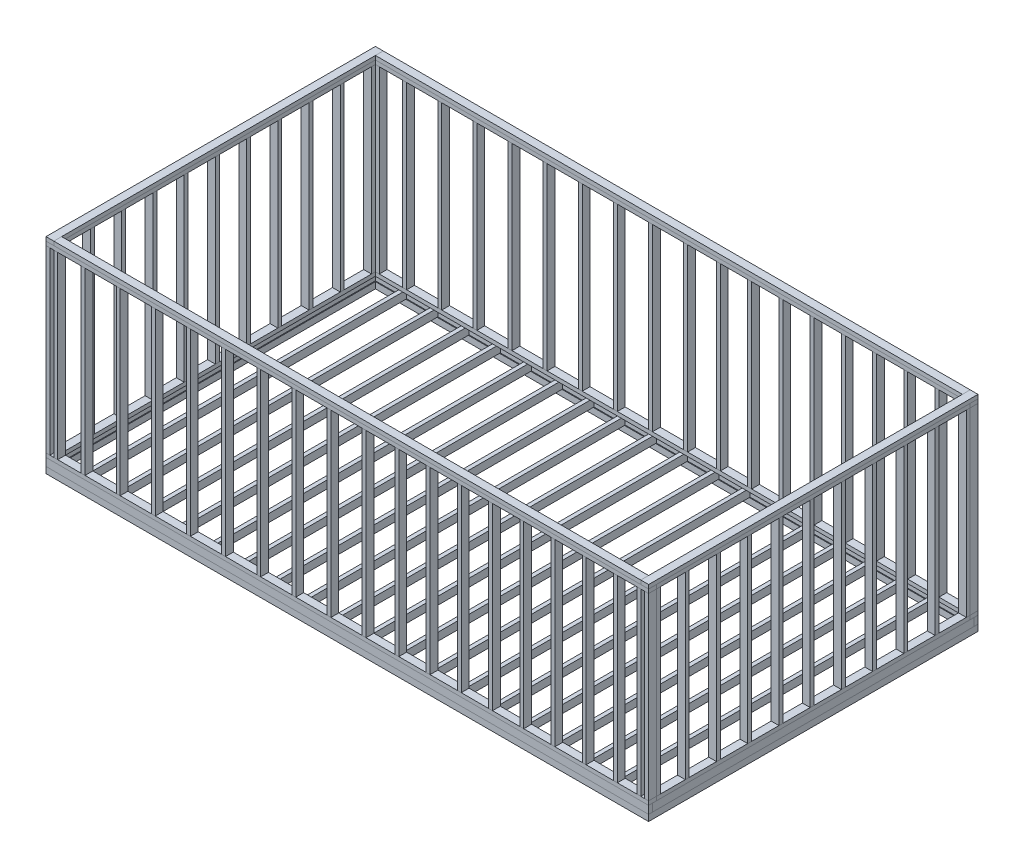
SolidWorks part; units mm, degrees
ref_plane "Front Plane" through (0, 0, 0) normal (0, 0, 1) x (1, 0, 0)
ref_plane "Top Plane" through (0, 0, 0) normal (0, 1, 0) x (1, 0, 0)
ref_plane "Right Plane" through (0, 0, 0) normal (1, 0, 0) x (0, 0, -1)
other "Configuration Table"
sketch "Metal Base" plane through (0, 0, 0) normal (0, 1, 0) x (1, 0, 0)
  line L1 (0, 0) -> (7600, 0)
  line L2 (0, 0) -> (0, 4100)
  line L3 (0, 4100) -> (7600, 4100)
  line L4 (7600, 0) -> (7600, 4100)
  dimension "D1" = 4100
  dimension "D2" = 7600
sketch "Furniture" plane through (0, 0, 0) normal (0, 1, 0) x (1, 0, 0)
  line L0 (6900, 2000) -> (6900, 4100)
  line L1 (2195.453, 2408.8005) -> (1395.453, 2408.8005)
  line L2 (2195.453, 2408.8005) -> (2195.453, 3908.8005)
  line L3 (2195.453, 3908.8005) -> (1395.453, 3908.8005)
  line L4 (1395.453, 2408.8005) -> (1395.453, 3908.8005)
  line L5 (1095.7475, 72.998) -> (95.7475, 72.998)
  line L6 (1095.7475, 72.998) -> (1095.7475, 2072.998)
  line L7 (1095.7475, 2072.998) -> (95.7475, 2072.998)
  line L8 (95.7475, 72.998) -> (95.7475, 2072.998)
  line L9 (0, 0) -> (0, 4100) construction
  line L10 (2300, 4100) -> (2300, 0)
  line L11 (0, 0) -> (7600, 0) construction
  line L12 (6400, 0) -> (6400, 2000)
  line L13 (0, 4100) -> (7600, 4100) construction
  line L14 (6400, 2000) -> (7600, 2000)
  line L15 (2300, 2050) -> (7946.9663, 2050) construction
  line L16 (7600, 0) -> (7600, 4100) construction
  line L17 (2079.5569, 869.0285) -> (2300, 100)
  line L18 (6400, 100) -> (6911.6082, 577.7625)
  line L19 (6590.3736, 1221.8512) -> (7190.3736, 1221.8512)
  line L24 (6590.3736, 1221.8512) -> (6590.3736, 1981.8512)
  line L25 (6590.3736, 1981.8512) -> (7190.3736, 1981.8512)
  line L26 (7190.3736, 1221.8512) -> (7190.3736, 1981.8512)
  line L27 (6400, 2000) -> (5800, 2000)
  line L28 (6400, 2000) -> (6400, 1400)
  line L29 (6400, 1400) -> (5800, 1400)
  line L30 (5800, 2000) -> (5800, 1400)
  line L31 (2300, 2050) -> (4300, 2050)
  line L32 (4300, 2050) -> (4300, 4100)
  line L33 (2300, 100) -> (2579.3532, 100) construction
  line L34 (2579.3532, 100) -> (2579.3532, 981.1813) construction
  line L35 (2579.3532, 981.1813) -> (2300, 981.1813) construction
  arc A1 (2079.5569, 869.0285) -> (1506.2746, 0) centre (2300, 100) ccw construction
  arc A2 (6911.6082, 577.7625) -> (6400, 800) centre (6400, 100) ccw construction
  dimension "D13" = 600
  dimension "D1" = 1500
  dimension "D2" = 800
  dimension "D3" = 2000
  dimension "D4" = 1000
  dimension "D5" = 2000
  dimension "D6" = 1200
  dimension "D7" = 700
  dimension "D8" = 600
  dimension "D9" = 2300
  dimension "D10" = 800
  dimension "D11" = 100
  dimension "D12" = 760
  dimension "D14" = 100
  dimension "D15" = 700
  dimension "D16" = 2100
  dimension "D17" = 600
  dimension "D18" = 4100
  dimension "D19" = 4100
  dimension "D20" = 2000
  dimension "D21" = 2050
sketch "Metal frame" plane through (0, 0, 0) normal (0, 1, 0) x (1, 0, 0)
  line L0 (0, 4100) -> (7600, 4100) construction
  line L1 (0, 4100) -> (7600, 4100)
  line L2 (0, 0) -> (0, 4100) construction
  line L3 (0, 0) -> (0, 4100)
  line L4 (0, 0) -> (7600, 0) construction
  line L5 (0, 0) -> (7600, 0)
  line L6 (7600, 0) -> (7600, 4100) construction
  line L7 (7600, 0) -> (7600, 4100)
  line L8 (-60, 4160) -> (7660, 4160)
  line L9 (7660, -60) -> (7660, 4160)
  line L10 (-60, -60) -> (7660, -60)
  line L11 (-60, -60) -> (-60, 4160)
  dimension "D2" = 7720
  dimension "D3" = 4220
  dimension "D1" = 60
sketch "Walls bottom" plane through (0, 0, 0) normal (0, 1, 0) x (1, 0, 0)
  line L0 (-60, 4160) -> (7660, 4160) construction
  line L2 (-60, -60) -> (7660, -60) construction
  line L3 (7660, -60) -> (7660, 4160) construction
  line L4 (-60, -60) -> (-60, 4160) construction
  line L5 (-60, -60) -> (7660, -60)
  line L6 (7660, -60) -> (7660, 4160)
  line L7 (-60, 4160) -> (7660, 4160)
  line L8 (-60, -60) -> (-60, 4160)
  line L9 (40, 40) -> (40, 4060)
  line L10 (40, 4060) -> (7560, 4060)
  line L11 (7560, 40) -> (7560, 4060)
  line L12 (40, 40) -> (7560, 40)
  dimension "D2" = 4020
  dimension "D3" = 7520
  dimension "D4" = 7720
  dimension "D5" = 4220
  dimension "D1" = 100
extrude "Boss-Extrude1" add sketch "Metal frame" against normal blind 80
sketch "Sketch4" plane through (0, 0, 0) normal (0, 1, 0) x (1, 0, 0)
  line L1 (-60, 4160) -> (7660, 4160)
  line L2 (-60, 4160) -> (-60, 4110)
  line L3 (-60, 4110) -> (7660, 4110)
  line L4 (7660, 4160) -> (7660, 4110)
  line L5 (7660, -60) -> (7660, 4160) construction
  line L7 (7660, 4110) -> (7610, 4110)
  line L8 (7660, 4110) -> (7660, -10)
  line L9 (7660, -10) -> (7610, -10)
  line L10 (7610, 4110) -> (7610, -10)
  line L11 (7660, -10) -> (-60, -10)
  line L12 (7660, -10) -> (7660, -60)
  line L13 (7660, -60) -> (-60, -60)
  line L14 (-60, -10) -> (-60, -60)
  line L15 (-60, -10) -> (-10, -10)
  line L16 (-60, -10) -> (-60, 4110)
  line L17 (-60, 4110) -> (-10, 4110)
  line L18 (-10, -10) -> (-10, 4110)
  line M13 (-60, 4160) -> (-60, -60)
  line M14 (-60, -60) -> (7660, -60)
  line M15 (7660, -60) -> (7660, 4160)
  line M16 (7660, 4160) -> (-60, 4160)
  dimension "D1" = 50
  dimension "D2" = 50
  dimension "D3" = 50
  dimension "D4" = 50
extrude "Boss-Extrude2" add sketch "Sketch4" along normal blind 100 separate body contours L3 M13 M15 M16 | L9 L11 M13 M14 M15 region at (3800, 0, -4135) region at (3800, 0, 35)
extrude "Boss-Extrude3" add sketch "Sketch4<3>" along normal blind 100 separate body contours L11 L18 L3 M13 | L3 L10 L9 M15 region at (-35, 0, -2050) region at (7635, 0, -2050)
sketch "Sketch4<3>" plane through (0, 0, 0) normal (0, 1, 0) x (1, 0, 0) same geometry as "Sketch4"
pattern_linear "LPattern1" count 20 spacing 400 along (1, 0, 0) of bodies 106
sketch "Sketch5" plane through (0, 100, 0) normal (0, 1, 0) x (1, 0, 0)
  line L0 (7660, -10) -> (7660, 4110) construction
  line L1 (-60, 4160) -> (7660, 4160)
  line L2 (-60, 4160) -> (-60, 4060)
  line L3 (-60, 4060) -> (7660, 4060)
  line L4 (7660, 4160) -> (7660, 4060)
  line L10 (7660, 4060) -> (7560, 4060)
  line L11 (7660, 4060) -> (7660, 40)
  line L12 (7660, 40) -> (7560, 40)
  line L13 (7560, 4060) -> (7560, 40)
  line L14 (-60, 4060) -> (40, 4060)
  line L15 (-60, 4060) -> (-60, 40)
  line L16 (-60, 40) -> (40, 40)
  line L17 (40, 4060) -> (40, 40)
  line L18 (-60, -60) -> (7660, -60)
  line L19 (-60, -60) -> (-60, 40)
  line L20 (-60, 40) -> (7660, 40)
  line L21 (7660, -60) -> (7660, 40)
  line M9 (7660, -10) -> (-60, -10)
  line M10 (-60, -10) -> (-60, -60)
  line M11 (-60, -60) -> (7660, -60)
  line M12 (7660, -60) -> (7660, -10)
  dimension "D1" = 100
  dimension "D2" = 100
  dimension "D3" = 100
  dimension "D4" = 100
extrude "Boss-Extrude4" add sketch "Sketch5" along normal blind 50 separate body contours L21 L12 L20 L16 L19 M9 | M12 M9 M10 M11 | L4 L1 L2 L3 region at (3800, 100, -4110) region at (3800, 100, -15) region at (3800, 100, 35)
extrude "Boss-Extrude5" add sketch "Sketch5<4>" along normal blind 50 separate body contours L3 L13 L12 L11 | L17 L3 L15 L16 region at (-10, 100, -2050) region at (7610, 100, -2050)
sketch "Sketch5<4>" plane through (0, 100, 0) normal (0, 1, 0) x (1, 0, 0) same geometry as "Sketch5"
sketch "Sketch6" plane through (0, 150, 0) normal (0, 1, 0) x (1, 0, 0)
  line L0 (7660, 40) -> (-60, 40) construction
  line L1 (-60, -60) -> (-10, -60)
  line L2 (-60, -60) -> (-60, 40)
  line L3 (-60, 40) -> (-10, 40)
  line L4 (-10, -60) -> (-10, 40)
  line L5 (-60, 4060) -> (40, 4060) construction
  line L6 (-60, 4160) -> (-10, 4160)
  line L7 (-60, 4160) -> (-60, 4060)
  line L8 (-60, 4060) -> (-10, 4060)
  line L9 (-10, 4160) -> (-10, 4060)
  line L10 (390, -60) -> (390, 40)
  line L11 (390, -60) -> (440, -60)
  line L12 (440, -60) -> (440, 40)
  line L13 (390, 40) -> (440, 40)
  line L14 (390, 4160) -> (390, 4060)
  line L15 (390, 4160) -> (440, 4160)
  line L16 (440, 4160) -> (440, 4060)
  line L17 (390, 4060) -> (440, 4060)
  line L18 (840, -60) -> (840, 40)
  line L19 (840, -60) -> (890, -60)
  line L20 (890, -60) -> (890, 40)
  line L21 (840, 40) -> (890, 40)
  line L22 (840, 4160) -> (840, 4060)
  line L23 (840, 4160) -> (890, 4160)
  line L24 (890, 4160) -> (890, 4060)
  line L25 (840, 4060) -> (890, 4060)
  line L26 (1290, -60) -> (1290, 40)
  line L27 (1290, -60) -> (1340, -60)
  line L28 (1340, -60) -> (1340, 40)
  line L29 (1290, 40) -> (1340, 40)
  line L30 (1290, 4160) -> (1290, 4060)
  line L31 (1290, 4160) -> (1340, 4160)
  line L32 (1340, 4160) -> (1340, 4060)
  line L33 (1290, 4060) -> (1340, 4060)
  line L34 (1740, -60) -> (1740, 40)
  line L35 (1740, -60) -> (1790, -60)
  line L36 (1790, -60) -> (1790, 40)
  line L37 (1740, 40) -> (1790, 40)
  line L38 (1740, 4160) -> (1740, 4060)
  line L39 (1740, 4160) -> (1790, 4160)
  line L40 (1790, 4160) -> (1790, 4060)
  line L41 (1740, 4060) -> (1790, 4060)
  line L42 (2190, -60) -> (2190, 40)
  line L43 (2190, -60) -> (2240, -60)
  line L44 (2240, -60) -> (2240, 40)
  line L45 (2190, 40) -> (2240, 40)
  line L46 (2190, 4160) -> (2190, 4060)
  line L47 (2190, 4160) -> (2240, 4160)
  line L48 (2240, 4160) -> (2240, 4060)
  line L49 (2190, 4060) -> (2240, 4060)
  line L50 (2640, -60) -> (2640, 40)
  line L51 (2640, -60) -> (2690, -60)
  line L52 (2690, -60) -> (2690, 40)
  line L53 (2640, 40) -> (2690, 40)
  line L54 (2640, 4160) -> (2640, 4060)
  line L55 (2640, 4160) -> (2690, 4160)
  line L56 (2690, 4160) -> (2690, 4060)
  line L57 (2640, 4060) -> (2690, 4060)
  line L58 (3090, -60) -> (3090, 40)
  line L59 (3090, -60) -> (3140, -60)
  line L60 (3140, -60) -> (3140, 40)
  line L61 (3090, 40) -> (3140, 40)
  line L62 (3090, 4160) -> (3090, 4060)
  line L63 (3090, 4160) -> (3140, 4160)
  line L64 (3140, 4160) -> (3140, 4060)
  line L65 (3090, 4060) -> (3140, 4060)
  line L66 (3540, -60) -> (3540, 40)
  line L67 (3540, -60) -> (3590, -60)
  line L68 (3590, -60) -> (3590, 40)
  line L69 (3540, 40) -> (3590, 40)
  line L70 (3540, 4160) -> (3540, 4060)
  line L71 (3540, 4160) -> (3590, 4160)
  line L72 (3590, 4160) -> (3590, 4060)
  line L73 (3540, 4060) -> (3590, 4060)
  line L74 (3990, -60) -> (3990, 40)
  line L75 (3990, -60) -> (4040, -60)
  line L76 (4040, -60) -> (4040, 40)
  line L77 (3990, 40) -> (4040, 40)
  line L78 (3990, 4160) -> (3990, 4060)
  line L79 (3990, 4160) -> (4040, 4160)
  line L80 (4040, 4160) -> (4040, 4060)
  line L81 (3990, 4060) -> (4040, 4060)
  line L82 (7560, 4060) -> (7660, 4060) construction
  line L83 (7660, 4160) -> (7610, 4160)
  line L84 (7660, 4160) -> (7660, 4060)
  line L85 (7660, 4060) -> (7610, 4060)
  line L86 (7610, 4160) -> (7610, 4060)
  line L87 (7660, 40) -> (7560, 40) construction
  line L88 (7660, -60) -> (7610, -60)
  line L89 (7660, -60) -> (7660, 40)
  line L90 (7660, 40) -> (7610, 40)
  line L91 (7610, -60) -> (7610, 40)
  line L92 (7260, -60) -> (7260, 40)
  line L93 (7260, -60) -> (7210, -60)
  line L94 (7210, -60) -> (7210, 40)
  line L95 (7260, 40) -> (7210, 40)
  line L96 (7260, 4160) -> (7260, 4060)
  line L97 (7260, 4160) -> (7210, 4160)
  line L98 (7210, 4160) -> (7210, 4060)
  line L99 (7260, 4060) -> (7210, 4060)
  line L100 (6860, -60) -> (6860, 40)
  line L101 (6860, -60) -> (6810, -60)
  line L102 (6810, -60) -> (6810, 40)
  line L103 (6860, 40) -> (6810, 40)
  line L104 (6860, 4160) -> (6860, 4060)
  line L105 (6860, 4160) -> (6810, 4160)
  line L106 (6810, 4160) -> (6810, 4060)
  line L107 (6860, 4060) -> (6810, 4060)
  line L108 (6460, -60) -> (6460, 40)
  line L109 (6460, -60) -> (6410, -60)
  line L110 (6410, -60) -> (6410, 40)
  line L111 (6460, 40) -> (6410, 40)
  line L112 (6460, 4160) -> (6460, 4060)
  line L113 (6460, 4160) -> (6410, 4160)
  line L114 (6410, 4160) -> (6410, 4060)
  line L115 (6460, 4060) -> (6410, 4060)
  line L116 (6060, -60) -> (6060, 40)
  line L117 (6060, -60) -> (6010, -60)
  line L118 (6010, -60) -> (6010, 40)
  line L119 (6060, 40) -> (6010, 40)
  line L120 (6060, 4160) -> (6060, 4060)
  line L121 (6060, 4160) -> (6010, 4160)
  line L122 (6010, 4160) -> (6010, 4060)
  line L123 (6060, 4060) -> (6010, 4060)
  line L124 (5660, -60) -> (5660, 40)
  line L125 (5660, -60) -> (5610, -60)
  line L126 (5610, -60) -> (5610, 40)
  line L127 (5660, 40) -> (5610, 40)
  line L128 (5660, 4160) -> (5660, 4060)
  line L129 (5660, 4160) -> (5610, 4160)
  line L130 (5610, 4160) -> (5610, 4060)
  line L131 (5660, 4060) -> (5610, 4060)
  line L132 (5260, -60) -> (5260, 40)
  line L133 (5260, -60) -> (5210, -60)
  line L134 (5210, -60) -> (5210, 40)
  line L135 (5260, 40) -> (5210, 40)
  line L136 (5260, 4160) -> (5260, 4060)
  line L137 (5260, 4160) -> (5210, 4160)
  line L138 (5210, 4160) -> (5210, 4060)
  line L139 (5260, 4060) -> (5210, 4060)
  line L140 (4860, -60) -> (4860, 40)
  line L141 (4860, -60) -> (4810, -60)
  line L142 (4810, -60) -> (4810, 40)
  line L143 (4860, 40) -> (4810, 40)
  line L144 (4860, 4160) -> (4860, 4060)
  line L145 (4860, 4160) -> (4810, 4160)
  line L146 (4810, 4160) -> (4810, 4060)
  line L147 (4860, 4060) -> (4810, 4060)
  line L148 (4460, -60) -> (4460, 40)
  line L149 (4460, -60) -> (4410, -60)
  line L150 (4410, -60) -> (4410, 40)
  line L151 (4460, 40) -> (4410, 40)
  line L152 (4460, 4160) -> (4460, 4060)
  line L153 (4460, 4160) -> (4410, 4160)
  line L154 (4410, 4160) -> (4410, 4060)
  line L155 (4460, 4060) -> (4410, 4060)
  dimension "D1" = 50
  dimension "D2" = 10
  dimension "D3" = 9
extrude "Boss-Extrude6" add sketch "Sketch6" along normal blind 2300 separate body
sketch "Sketch7" plane through (0, 150, 0) normal (0, 1, 0) x (1, 0, 0)
  line L0 (40, 4060) -> (40, 40) construction
  line L1 (-60, 4060) -> (40, 4060)
  line L2 (-60, 4060) -> (-60, 4010)
  line L3 (-60, 4010) -> (40, 4010)
  line L4 (40, 4060) -> (40, 4010)
  line L5 (7660, 4060) -> (7660, 40) construction
  line L6 (7560, 4060) -> (7660, 4060)
  line L7 (7560, 4060) -> (7560, 4010)
  line L8 (7560, 4010) -> (7660, 4010)
  line L9 (7660, 4060) -> (7660, 4010)
  line L10 (-60, 3660) -> (-60, 3610)
  line L11 (-60, 3660) -> (40, 3660)
  line L12 (40, 3660) -> (40, 3610)
  line L13 (-60, 3610) -> (40, 3610)
  line L14 (7560, 3660) -> (7560, 3610)
  line L15 (7560, 3660) -> (7660, 3660)
  line L16 (7660, 3660) -> (7660, 3610)
  line L17 (7560, 3610) -> (7660, 3610)
  line L18 (-60, 3260) -> (-60, 3210)
  line L19 (-60, 3260) -> (40, 3260)
  line L20 (40, 3260) -> (40, 3210)
  line L21 (-60, 3210) -> (40, 3210)
  line L22 (7560, 3260) -> (7560, 3210)
  line L23 (7560, 3260) -> (7660, 3260)
  line L24 (7660, 3260) -> (7660, 3210)
  line L25 (7560, 3210) -> (7660, 3210)
  line L26 (-60, 2860) -> (-60, 2810)
  line L27 (-60, 2860) -> (40, 2860)
  line L28 (40, 2860) -> (40, 2810)
  line L29 (-60, 2810) -> (40, 2810)
  line L30 (7560, 2860) -> (7560, 2810)
  line L31 (7560, 2860) -> (7660, 2860)
  line L32 (7660, 2860) -> (7660, 2810)
  line L33 (7560, 2810) -> (7660, 2810)
  line L34 (-60, 2460) -> (-60, 2410)
  line L35 (-60, 2460) -> (40, 2460)
  line L36 (40, 2460) -> (40, 2410)
  line L37 (-60, 2410) -> (40, 2410)
  line L38 (7560, 2460) -> (7560, 2410)
  line L39 (7560, 2460) -> (7660, 2460)
  line L40 (7660, 2460) -> (7660, 2410)
  line L41 (7560, 2410) -> (7660, 2410)
  line L42 (-60, 2060) -> (-60, 2010)
  line L43 (-60, 2060) -> (40, 2060)
  line L44 (40, 2060) -> (40, 2010)
  line L45 (-60, 2010) -> (40, 2010)
  line L46 (7560, 2060) -> (7560, 2010)
  line L47 (7560, 2060) -> (7660, 2060)
  line L48 (7660, 2060) -> (7660, 2010)
  line L49 (7560, 2010) -> (7660, 2010)
  line L50 (-60, 1660) -> (-60, 1610)
  line L51 (-60, 1660) -> (40, 1660)
  line L52 (40, 1660) -> (40, 1610)
  line L53 (-60, 1610) -> (40, 1610)
  line L54 (7560, 1660) -> (7560, 1610)
  line L55 (7560, 1660) -> (7660, 1660)
  line L56 (7660, 1660) -> (7660, 1610)
  line L57 (7560, 1610) -> (7660, 1610)
  line L58 (-60, 1260) -> (-60, 1210)
  line L59 (-60, 1260) -> (40, 1260)
  line L60 (40, 1260) -> (40, 1210)
  line L61 (-60, 1210) -> (40, 1210)
  line L62 (7560, 1260) -> (7560, 1210)
  line L63 (7560, 1260) -> (7660, 1260)
  line L64 (7660, 1260) -> (7660, 1210)
  line L65 (7560, 1210) -> (7660, 1210)
  line L66 (-60, 860) -> (-60, 810)
  line L67 (-60, 860) -> (40, 860)
  line L68 (40, 860) -> (40, 810)
  line L69 (-60, 810) -> (40, 810)
  line L70 (7560, 860) -> (7560, 810)
  line L71 (7560, 860) -> (7660, 860)
  line L72 (7660, 860) -> (7660, 810)
  line L73 (7560, 810) -> (7660, 810)
  line L74 (-60, 460) -> (-60, 410)
  line L75 (-60, 460) -> (40, 460)
  line L76 (40, 460) -> (40, 410)
  line L77 (-60, 410) -> (40, 410)
  line L78 (7560, 460) -> (7560, 410)
  line L79 (7560, 460) -> (7660, 460)
  line L80 (7660, 460) -> (7660, 410)
  line L81 (7560, 410) -> (7660, 410)
  dimension "D1" = 50
  dimension "D2" = 10
extrude "Boss-Extrude7" add sketch "Sketch7" along normal blind 2300 separate body
sketch "Sketch8" plane through (0, 150, 0) normal (0, 1, 0) x (1, 0, 0)
  line L0 (40, 4060) -> (40, 40) construction
  line L1 (-60, 40) -> (40, 40)
  line L2 (-60, 40) -> (-60, 90)
  line L3 (-60, 90) -> (40, 90)
  line L4 (40, 40) -> (40, 90)
  line L5 (7560, 4060) -> (7560, 40) construction
  line L6 (7660, 40) -> (7560, 40)
  line L7 (7660, 40) -> (7660, 90)
  line L8 (7660, 90) -> (7560, 90)
  line L9 (7560, 40) -> (7560, 90)
  line L10 (-60, -60) -> (7660, -60) construction
  line L11 (7560, 40) -> (7510, 40)
  line L12 (7560, 40) -> (7560, -60)
  line L13 (7560, -60) -> (7510, -60)
  line L14 (7510, 40) -> (7510, -60)
  line L15 (-60, 4160) -> (7660, 4160) construction
  line L16 (40, 40) -> (90, 40)
  line L17 (40, 40) -> (40, -60)
  line L18 (40, -60) -> (90, -60)
  line L19 (90, 40) -> (90, -60)
  line L20 (40, 4060) -> (90, 4060)
  line L21 (40, 4060) -> (40, 4160)
  line L22 (40, 4160) -> (90, 4160)
  line L23 (90, 4060) -> (90, 4160)
  line L25 (7560, 4060) -> (7510, 4060)
  line L26 (7560, 4060) -> (7560, 4160)
  line L27 (7560, 4160) -> (7510, 4160)
  line L28 (7510, 4060) -> (7510, 4160)
  line M9 (40, 40) -> (40, 4060)
  line M11 (-60, 4060) -> (-60, 40)
  line M12 (-60, 40) -> (40, 40)
extrude "Boss-Extrude8" add sketch "Sketch8" along normal blind 2300 separate body contours L20 L23 L22 L21 | L3 M11 M12 M9 | L19 L16 L17 L18 | L11 L14 L13 L12 | L9 L6 L7 L8 | L28 L25 L26 L27 region at (-10, 150, -65) region at (65, 150, -4110) region at (65, 150, 10) region at (7535, 150, 10) region at (7610, 150, -65) region at (7535, 150, -4110)
sketch "Sketch9" plane through (0, 2450, 0) normal (0, 1, 0) x (1, 0, 0)
  line L1 (-60, 4060) -> (40, 4060)
  line L2 (-60, 4060) -> (-60, 40)
  line L3 (-60, 40) -> (40, 40)
  line L4 (40, 4060) -> (40, 40)
  line L5 (7560, 4060) -> (7660, 4060)
  line L6 (7560, 4060) -> (7560, 40)
  line L7 (7560, 40) -> (7660, 40)
  line L8 (7660, 4060) -> (7660, 40)
extrude "Boss-Extrude9" add sketch "Sketch9" along normal blind 50 separate body
sketch "Sketch10" plane through (0, 2450, 0) normal (0, 1, 0) x (1, 0, 0)
  line L1 (-60, 4160) -> (7660, 4160)
  line L2 (-60, 4160) -> (-60, 4060)
  line L3 (-60, 4060) -> (7660, 4060)
  line L4 (7660, 4160) -> (7660, 4060)
  line L5 (-60, 40) -> (7660, 40)
  line L6 (-60, 40) -> (-60, -60)
  line L7 (-60, -60) -> (7660, -60)
  line L8 (7660, 40) -> (7660, -60)
extrude "Boss-Extrude10" add sketch "Sketch10" along normal blind 50 separate body
sketch "Sketch11" plane through (0, 2500, 0) normal (0, 1, 0) x (1, 0, 0)
  line L1 (-60, 4160) -> (40, 4160)
  line L2 (-60, 4160) -> (-60, -60)
  line L3 (-60, -60) -> (40, -60)
  line L4 (40, 4160) -> (40, -60)
  line L5 (7660, 4160) -> (7560, 4160)
  line L6 (7660, 4160) -> (7660, -60)
  line L7 (7660, -60) -> (7560, -60)
  line L8 (7560, 4160) -> (7560, -60)
  line M2 (-60, 4060) -> (7660, 4060)
  line M4 (7660, 4160) -> (-60, 4160)
extrude "Boss-Extrude11" add sketch "Sketch11" along normal blind 50 separate body
extrude "Boss-Extrude12" add sketch "Sketch11<3>" along normal blind 50 separate body contours L8 L4 M4 M2 region at (3800, 2500, -4110)
sketch "Sketch11<3>" plane through (0, 2500, 0) normal (0, 1, 0) x (1, 0, 0) same geometry as "Sketch11"
sketch "Sketch12" plane through (0, 2500, 0) normal (0, 1, 0) x (1, 0, 0)
  line L1 (40, 40) -> (7560, 40)
  line L2 (40, 40) -> (40, -60)
  line L3 (40, -60) -> (7560, -60)
  line L4 (7560, 40) -> (7560, -60)
extrude "Boss-Extrude13" add sketch "Sketch12" along normal blind 50 separate body
